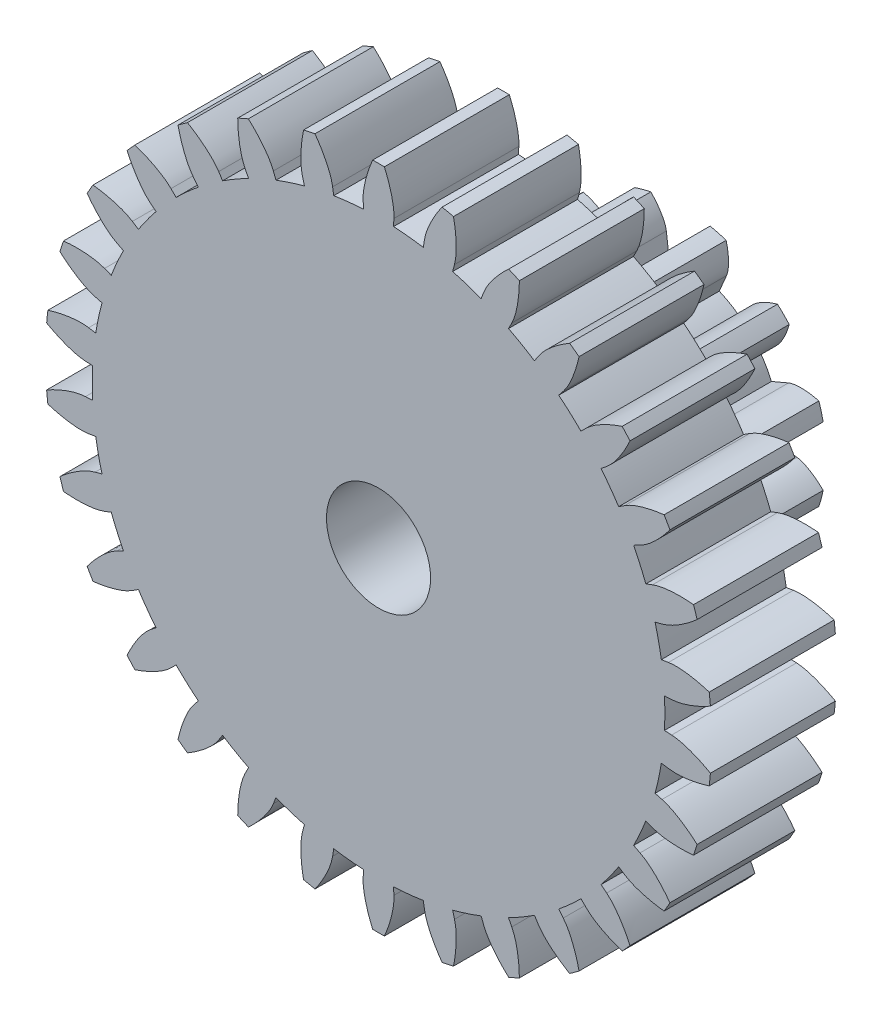
SolidWorks part; units mm, degrees
ref_plane "前视基准面" through (0, 0, 0) normal (0, 0, 1) x (1, 0, 0)
ref_plane "上视基准面" through (0, 0, 0) normal (0, 1, 0) x (1, 0, 0)
ref_plane "右视基准面" through (0, 0, 0) normal (1, 0, 0) x (0, 0, -1)
other "Configuration Table"
sketch "草图1" plane through (0, 0, 0) normal (0, 0, 1) x (1, 0, 0)
  line L0 (0, 0) -> (1.2, 0) construction
  line L1 (0, 0) -> (1.1897, 0.1566) construction
  line L2 (0, 0) -> (1.1195, 0.1354)
  line L3 (1.1897, 0.1566) -> (1.1897, -0.1566) construction
  line L4 (0, 0) -> (1.1195, -0.1354)
  circle A0 centre (0, 0) radius 1.4
  circle A1 centre (0, 0) radius 1.2 construction
  circle A2 centre (0, 0) radius 0.95
  circle A3 centre (0, 0) radius 1.1276 construction
  circle A4 centre (0, 0) radius 0.5
  spline S0 degree 4 poles (1.1195, 0.1354) (1.128, 0.1365) (1.1516, 0.1411) (1.1949, 0.157) (1.2609, 0.1921) (1.3385, 0.2504) (1.4265, 0.3386) (1.513, 0.4563) (1.5884, 0.5979) (1.6479, 0.7602) (1.6868, 0.9286) (1.7064, 1.1002) (1.7082, 1.2814) (1.6868, 1.5048) (1.6275, 1.7661) (1.5147, 2.0566) (1.3415, 2.356) (1.1264, 2.6272) (0.878, 2.867) (0.599, 3.0728) (0.3008, 3.2436) (-0.0211, 3.378) (-0.346, 3.4768) (-0.6967, 3.5387) (-0.9642, 3.5622) (-1.2659, 3.561) (-1.4376, 3.5485) (-1.6326, 3.5286) (-1.737, 3.508) (-1.8243, 3.4941) (-1.8493, 3.4877) (-1.868, 3.4841) knots 0 0 0 0 0 0.005604 0.015718 0.02996 0.048734 0.068727 0.096889 0.125051 0.153212 0.181374 0.209535 0.237696 0.271429 0.327752 0.384075 0.440398 0.496721 0.553044 0.609367 0.66569 0.722013 0.778336 0.834659 0.890982 0.909091 0.954545 0.977273 0.988636 1 1 1 1 1 construction
  spline S1 degree 4 poles (1.1195, 0.1354) (1.128, 0.1365) (1.1516, 0.1411) (1.1949, 0.157) (1.2609, 0.1921) (1.3385, 0.2504) (1.4265, 0.3386) (1.513, 0.4563) (1.5884, 0.5979) (1.6479, 0.7602) (1.6868, 0.9286) (1.7064, 1.1002) (1.7082, 1.2814) (1.6868, 1.5048) (1.6275, 1.7661) (1.5147, 2.0566) (1.3415, 2.356) (1.1264, 2.6272) (0.878, 2.867) (0.599, 3.0728) (0.3008, 3.2436) (-0.0211, 3.378) (-0.346, 3.4768) (-0.6967, 3.5387) (-0.9642, 3.5622) (-1.1881, 3.5613) (-1.292, 3.5571) (-1.3172, 3.5557) knots 0 0 0 0 0 0.005604 0.015718 0.02996 0.048734 0.068727 0.096889 0.125051 0.153212 0.181374 0.209535 0.237696 0.271429 0.327752 0.384075 0.440398 0.496721 0.553044 0.609367 0.66569 0.722013 0.778336 0.834659 0.890982 0.909091 0.909091 0.909091 0.909091 0.909091
  spline S2 degree 4 poles (1.1195, -0.1354) (1.128, -0.1365) (1.1516, -0.1411) (1.1949, -0.157) (1.2609, -0.1921) (1.3385, -0.2504) (1.4265, -0.3386) (1.513, -0.4563) (1.5884, -0.5979) (1.6479, -0.7602) (1.6868, -0.9286) (1.7064, -1.1002) (1.7082, -1.2814) (1.6868, -1.5048) (1.6275, -1.7661) (1.5147, -2.0566) (1.3415, -2.356) (1.1264, -2.6272) (0.878, -2.867) (0.599, -3.0728) (0.3008, -3.2436) (-0.0211, -3.378) (-0.346, -3.4768) (-0.6967, -3.5387) (-0.9642, -3.5622) (-1.2659, -3.561) (-1.4376, -3.5485) (-1.6326, -3.5286) (-1.737, -3.508) (-1.8243, -3.4941) (-1.8493, -3.4877) (-1.868, -3.4841) knots 0 0 0 0 0 0.005604 0.015718 0.02996 0.048734 0.068727 0.096889 0.125051 0.153212 0.181374 0.209535 0.237696 0.271429 0.327752 0.384075 0.440398 0.496721 0.553044 0.609367 0.66569 0.722013 0.778336 0.834659 0.890982 0.909091 0.954545 0.977273 0.988636 1 1 1 1 1 construction
  spline S3 degree 4 poles (1.1195, -0.1354) (1.128, -0.1365) (1.1516, -0.1411) (1.1949, -0.157) (1.2609, -0.1921) (1.3385, -0.2504) (1.4265, -0.3386) (1.513, -0.4563) (1.5884, -0.5979) (1.6479, -0.7602) (1.6868, -0.9286) (1.7064, -1.1002) (1.7082, -1.2814) (1.6868, -1.5048) (1.6275, -1.7661) (1.5147, -2.0566) (1.3415, -2.356) (1.1264, -2.6272) (0.878, -2.867) (0.599, -3.0728) (0.3008, -3.2436) (-0.0211, -3.378) (-0.346, -3.4768) (-0.6967, -3.5387) (-0.9642, -3.5622) (-1.1881, -3.5613) (-1.292, -3.5571) (-1.3172, -3.5557) knots 0 0 0 0 0 0.005604 0.015718 0.02996 0.048734 0.068727 0.096889 0.125051 0.153212 0.181374 0.209535 0.237696 0.271429 0.327752 0.384075 0.440398 0.496721 0.553044 0.609367 0.66569 0.722013 0.778336 0.834659 0.890982 0.909091 0.909091 0.909091 0.909091 0.909091
  point P15 (1.1897, 0)
  dimension "齿顶圆直径" = 2.8
  dimension "分度圆直径" = 2.4
  dimension "齿根圆直径" = 1.9
  dimension "基圆直径" = 2.2553
  dimension "内孔直径" = 1
  dimension "渐近线镜像线夹角" = 7.5
extrude "凸台-拉伸1" add sketch "草图1" along normal blind 1.7 contours A0 | A4
extrude "切除-拉伸1" cut sketch "草图1<3>" along normal through all contours A2 S3 A0 S1 region at (1.2063, 0, 0)
sketch "草图1<3>" plane through (0, 0, 0) normal (0, 0, 1) x (1, 0, 0) same geometry as "草图1"
pattern_circular "阵列(圆周)1" count 12 every 30 about axis through (0, 0, 1.7) along (0, 0, 1) of "切除-拉伸1"
sketch "草图2" plane through (0, 0, 1.7) normal (0, 0, 1) x (1, 0, 0)
  line L0 (0, 0) -> (3, 0) construction
  line L1 (0, 0) -> (2.8152, 0.1475)
  line L2 (0, 0) -> (2.8152, -0.1475)
  line L3 (2.8152, 0.1475) -> (2.8152, -0.1475) construction
  circle A0 centre (0, 0) radius 3 construction
  circle A1 centre (0, 0) radius 2.8191 construction
  circle A2 centre (0, 0) radius 2.75
  circle A3 centre (0, 0) radius 3.2
  circle A4 centre (0, 0) radius 0.5
  spline S0 degree 4 poles (2.8152, -0.1475) (2.8367, -0.1487) (2.8963, -0.1563) (3.0071, -0.1885) (3.1777, -0.2648) (3.3811, -0.397) (3.6155, -0.602) (3.8513, -0.881) (4.0635, -1.2213) (4.2394, -1.6162) (4.365, -2.0294) (4.4433, -2.4541) (4.4782, -2.9057) (4.4631, -3.4665) (4.3592, -4.1285) (4.1278, -4.8721) (3.7457, -5.6484) (3.257, -6.3614) (2.6755, -7.0016) (2.0192, -7.5623) (1.2967, -8.0391) (0.5293, -8.429) (-0.2857, -8.7309) (-1.0078, -8.9177) (-1.6623, -9.0235) (-2.1343, -9.0715) (-2.5561, -9.092) (-2.8357, -9.0955) (-3.23, -9.0889) (-3.5275, -9.0667) (-3.825, -9.0413) (-3.9743, -9.0192) (-4.0706, -9.0075) knots 0 0 0 0 0 0.005604 0.015718 0.02996 0.048734 0.068727 0.096889 0.125051 0.153212 0.181374 0.209535 0.237696 0.271429 0.327752 0.384075 0.440398 0.496721 0.553044 0.609367 0.66569 0.722013 0.778336 0.834659 0.86282 0.890982 0.909091 0.931818 0.954545 0.977273 1 1 1 1 1 construction
  spline S1 degree 4 poles (2.8152, -0.1475) (2.8367, -0.1487) (2.8963, -0.1563) (3.0071, -0.1885) (3.1777, -0.2648) (3.3811, -0.397) (3.6155, -0.602) (3.8513, -0.881) (4.0635, -1.2213) (4.2394, -1.6162) (4.365, -2.0294) (4.4433, -2.4541) (4.4782, -2.9057) (4.4631, -3.4665) (4.3592, -4.1285) (4.1278, -4.8721) (3.7457, -5.6484) (3.257, -6.3614) (2.6755, -7.0016) (2.0192, -7.5623) (1.2967, -8.0391) (0.5293, -8.429) (-0.2857, -8.7309) (-1.0078, -8.9177) (-1.6623, -9.0235) (-2.1343, -9.0715) (-2.4574, -9.0872) (-2.6182, -9.0916) (-2.6811, -9.0926) knots 0 0 0 0 0 0.005604 0.015718 0.02996 0.048734 0.068727 0.096889 0.125051 0.153212 0.181374 0.209535 0.237696 0.271429 0.327752 0.384075 0.440398 0.496721 0.553044 0.609367 0.66569 0.722013 0.778336 0.834659 0.86282 0.890982 0.909091 0.909091 0.909091 0.909091 0.909091
  spline S2 degree 4 poles (2.8152, 0.1475) (2.8367, 0.1487) (2.8963, 0.1563) (3.0071, 0.1885) (3.1777, 0.2648) (3.3811, 0.397) (3.6155, 0.602) (3.8513, 0.881) (4.0635, 1.2213) (4.2394, 1.6162) (4.365, 2.0294) (4.4433, 2.4541) (4.4782, 2.9057) (4.4631, 3.4665) (4.3592, 4.1285) (4.1278, 4.8721) (3.7457, 5.6484) (3.257, 6.3614) (2.6755, 7.0016) (2.0192, 7.5623) (1.2967, 8.0391) (0.5293, 8.429) (-0.2857, 8.7309) (-1.0078, 8.9177) (-1.6623, 9.0235) (-2.1343, 9.0715) (-2.5561, 9.092) (-2.8357, 9.0955) (-3.23, 9.0889) (-3.5275, 9.0667) (-3.825, 9.0413) (-3.9743, 9.0192) (-4.0706, 9.0075) knots 0 0 0 0 0 0.005604 0.015718 0.02996 0.048734 0.068727 0.096889 0.125051 0.153212 0.181374 0.209535 0.237696 0.271429 0.327752 0.384075 0.440398 0.496721 0.553044 0.609367 0.66569 0.722013 0.778336 0.834659 0.86282 0.890982 0.909091 0.931818 0.954545 0.977273 1 1 1 1 1 construction
  spline S3 degree 4 poles (2.8152, 0.1475) (2.8367, 0.1487) (2.8963, 0.1563) (3.0071, 0.1885) (3.1777, 0.2648) (3.3811, 0.397) (3.6155, 0.602) (3.8513, 0.881) (4.0635, 1.2213) (4.2394, 1.6162) (4.365, 2.0294) (4.4433, 2.4541) (4.4782, 2.9057) (4.4631, 3.4665) (4.3592, 4.1285) (4.1278, 4.8721) (3.7457, 5.6484) (3.257, 6.3614) (2.6755, 7.0016) (2.0192, 7.5623) (1.2967, 8.0391) (0.5293, 8.429) (-0.2857, 8.7309) (-1.0078, 8.9177) (-1.6623, 9.0235) (-2.1343, 9.0715) (-2.4574, 9.0872) (-2.6182, 9.0916) (-2.6811, 9.0926) knots 0 0 0 0 0 0.005604 0.015718 0.02996 0.048734 0.068727 0.096889 0.125051 0.153212 0.181374 0.209535 0.237696 0.271429 0.327752 0.384075 0.440398 0.496721 0.553044 0.609367 0.66569 0.722013 0.778336 0.834659 0.86282 0.890982 0.909091 0.909091 0.909091 0.909091 0.909091
  point P16 (2.8152, 0)
  dimension "内孔直径" = 1
  dimension "分度圆直径" = 6
  dimension "齿顶圆直径" = 6.4
  dimension "基圆直径" = 5.6382
  dimension "齿根圆直径" = 5.5
  dimension "渐开线镜像线夹角" = 3
extrude "凸台-拉伸2" add sketch "草图2" along normal blind 1.2 contours A3 | A4
extrude "切除-拉伸3" cut sketch "草图2<3>" along normal through all contours S3 L1 A2 L2 S1 A3 region at (2.9999, 0, 1.7)
sketch "草图2<3>" plane through (0, 0, 1.7) normal (0, 0, 1) x (1, 0, 0) same geometry as "草图2"
pattern_circular "阵列(圆周)2" count 30 over 360 about axis through (0, 0, 2.9) along (0, 0, 1) of "切除-拉伸3"
equation "\"m\"= 0.2'模数"
equation "\"z\"= 12'齿数"
equation "\"a\"= 20度'压力角"
equation "\"d\"= \"m\" * \"z\"'分度圆直径"
equation "\"da\"= ( \"z\" + 2 ) * \"m\"'齿顶圆直径"
equation "\"df\"= ( \"z\" - 2.5 ) * \"m\"'齿根圆直径"
equation "\"s\"= 0.5 * PI * \"m\"'分度圆齿厚"
equation "\"r\"= 0.38 * \"m\"'齿根圆角"
equation "\"B\"= 0.3 * \"d\"'齿厚"
equation "\"db\"= \"m\" * \"z\" * cos ( \"a\" )'基圆直径"
equation "\"rb\"= \"db\" / 2'基圆半径"
equation "\"齿顶圆直径@草图1\"= \"da\""
equation "\"分度圆直径@草图1\"= \"d\""
equation "\"齿根圆直径@草图1\"= \"df\""
equation "\"基圆直径@草图1\"= \"db\""
equation "\"渐近线镜像线夹角@草图1\"= 360 / 4 / \"z\""
equation "\"h\" = 1.7mm'齿轮厚度"
equation "\"ir\" = 1'内孔直径"
equation "\"内孔直径@草图1\"= \"ir\""
equation "\"齿轮厚@凸台-拉伸1\"= \"h\""
equation "\"齿轮夹角@阵列(圆周)1\"= 360 / \"z\""
equation "\"齿数@阵列(圆周)1\"= \"z\""
equation "\"m1\"= 0.2'模数"
equation "\"z1\" = 30'齿数"
equation "\"a1\"= 20度'压力角"
equation "\"d1\"= \"m1\" * \"z1\"'分度圆直径"
equation "\"da1\"= ( \"z1\" + 2 ) * \"m1\"'齿顶圆直径"
equation "\"df1\"= ( \"z1\" - 2.5 ) * \"m1\"'齿根圆直径"
equation "\"s1\"= 0.5 * PI * \"m1\"'分度圆齿厚"
equation "\"r1\"= 0.38 * \"m1\"'齿根圆角"
equation "\"B1\"= 0.3 * \"d1\"'齿厚"
equation "\"db1\"= \"m1\" * \"z1\" * cos ( \"a1\" )'基圆直径"
equation "\"rb1\"= \"db1\" / 2'基圆半径"
equation "\"分度圆直径@草图2\"= \"d1\""
equation "\"齿顶圆直径@草图2\"= \"da1\""
equation "\"基圆直径@草图2\"= \"db1\""
equation "\"齿根圆直径@草图2\"= \"df1\""
equation "\"渐开线镜像线夹角@草图2\"= 360 / 4 / \"z1\""
equation "\"内孔直径@草图2\"= \"ir\""
equation "\"二层齿轮厚@凸台-拉伸2\" = \"h1\""
equation "\"h1\"= 1.2'齿轮厚度"
equation "\"二层齿数@阵列(圆周)2\"= \"z1\""
